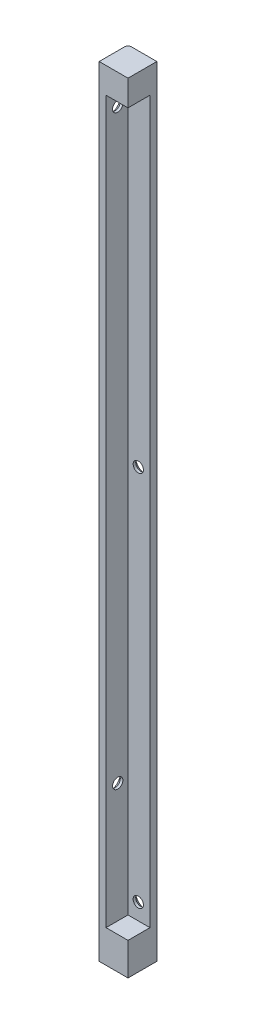
SolidWorks part; units mm, degrees
material "Aluminum"
ref_plane "Front Plane" through (0, 0, 0) normal (0, 0, 1) x (1, 0, 0)
ref_plane "Top Plane" through (0, 0, 0) normal (0, 1, 0) x (1, 0, 0)
ref_plane "Right Plane" through (0, 0, 0) normal (1, 0, 0) x (0, 0, -1)
sketch "Sketch1" plane through (0, 0, 0) normal (0, 1, 0) x (1, 0, 0)
  line L0 (0, 0) -> (0, 9)
  line L1 (0, 9) -> (9, 9)
  line L2 (2, 0) -> (2, 7)
  line L3 (2, 7) -> (9, 7)
  line L4 (9, 9) -> (9, 7)
  line L5 (0, 0) -> (2, 0)
  dimension "D1" = 9
  dimension "D2" = 9
  dimension "D3" = 2
extrude "Boss-Extrude1" add sketch "Sketch1" along normal blind 221.5
hole_wizard "CSK for M3 Countersunk Flat Head Screw1" positions "Sketch5" profile "Sketch4" countersink size "M3" standard "ISO" end condition through all
sketch "Sketch5" plane through (0, 0, 0) normal (-1, 0, 0) x (0, 0, 1)
  line L6 (-9, 221.5) -> (-9, 0) construction
  line L8 (-9, 110.75) -> (50.482, 110.75) construction
  point P16 (-4, 211)
  point P35 (-4, 40.25)
sketch "Sketch4" plane through (0, 211, -4) normal (0, 1, 0) x (0, 0, 1)
  line L0 (0, 0) -> (0, 9)
  line L1 (0, 9) -> (1.5, 9)
  line L2 (1.5, 9) -> (1.5, 1.25)
  line L3 (1.5, 1.25) -> (2.75, 0)
  line L5 (2.75, 0) -> (0, 0)
  line L6 (-1.5, 1.25) -> (-2.75, 0) construction
  line L11 (0, -6.35) -> (0, 107.95) construction
  dimension "Thru Hole Dia." = 3
  dimension "Thru Hole Depth" = 9
  dimension "Near C'Sink Dia." = 5.5
  dimension "Near C'Sink Angle" = 90
hole_wizard "CSK for M3 Countersunk Flat Head Screw4" positions "Sketch11" profile "Sketch10" countersink size "M3" standard "ISO" end condition through all
sketch "Sketch11" plane through (0, 0, -9) normal (0, 0, -1) x (-1, 0, 0)
  line L4 (0, 221.5) -> (0, 0) construction
  line L7 (0, 110.75) -> (77.647, 110.75) construction
  point P4 (-5, 10.25)
  point P33 (-5, 120)
sketch "Sketch10" plane through (5, 10.25, -9) normal (1, 0, 0) x (0, 1, 0)
  line L0 (0, 0) -> (0, 9)
  line L1 (0, 9) -> (1.5, 9)
  line L2 (1.5, 9) -> (1.5, 1.25)
  line L3 (1.5, 1.25) -> (2.75, 0)
  line L5 (2.75, 0) -> (0, 0)
  line L6 (-1.5, 1.25) -> (-2.75, 0) construction
  line L11 (0, -6.35) -> (0, 107.95) construction
  dimension "Thru Hole Dia." = 3
  dimension "Thru Hole Depth" = 9
  dimension "Near C'Sink Dia." = 5.5
  dimension "Near C'Sink Angle" = 90
sketch "Sketch12" plane through (0, 0, 0) normal (0, -1, 0) x (1, 0, 0)
  line L0 (2, -7) -> (9, -7) construction
  line L1 (1, -7) -> (9, -7)
  line L2 (1, -7) -> (1, 0)
  line L3 (1, 0) -> (9, 0)
  line L4 (9, -7) -> (9, 0)
  line L5 (9, -7) -> (9, -9) construction
extrude "Boss-Extrude2" add sketch "Sketch12" against normal blind 5.5
sketch "Sketch13" plane through (0, 221.5, 0) normal (0, 1, 0) x (1, 0, 0)
  line L0 (0, 8) -> (1, 9)
  line L1 (0, 9) -> (0, 0) construction
  line L2 (9, 9) -> (0, 9) construction
  line L3 (0, 8) -> (0, 9)
  line L4 (0, 9) -> (1, 9)
  dimension "D1" = 1
  dimension "D2" = 1
extrude "Cut-Extrude1" cut sketch "Sketch13" against normal blind 359
sketch "Sketch14" plane through (0, 0, 0) normal (0, -1, 0) x (1, 0, 0)
  line L0 (0, 0) -> (9, 0)
  line L1 (9, 0) -> (9, -9)
  line L2 (9, -9) -> (1, -9)
  line L3 (1, -9) -> (0, -8)
  line L4 (0, -8) -> (0, 0)
extrude "Boss-Extrude3" add sketch "Sketch14" along normal blind 3
sketch "Sketch18" plane through (0, 221.5, 0) normal (0, 1, 0) x (1, 0, 0)
  line L1 (0, 0) -> (9, 0)
  line L2 (0, 0) -> (0, 8)
  line L3 (1, 9) -> (9, 9)
  line L4 (9, 0) -> (9, 9)
  line L5 (1, 9) -> (0, 8)
  dimension "D1" = 9
  dimension "D2" = 9
extrude "Boss-Extrude4" add sketch "Sketch18" along normal blind 2.5 and the other way blind 6
sketch "Sketch19" plane through (0, 0, 0) normal (-1, 0, 0) x (0, 0, 1)
  line L1 (0, 224) -> (-0.6, 224)
  line L2 (0, 224) -> (0, -3)
  line L3 (0, -3) -> (-0.6, -3)
  line L4 (-0.6, 224) -> (-0.6, -3)
  line L5 (0, 224) -> (0, -3) construction
  dimension "D1" = 0.6
extrude "Cut-Extrude2" cut sketch "Sketch19" against normal blind 10
sketch "Sketch20" plane through (0, 0, 0) normal (-1, 0, 0) x (0, 0, 1)
  line L1 (-0.6, 224) -> (-16.2047, 224)
  line L2 (-0.6, 224) -> (-0.6, 222)
  line L3 (-0.6, 222) -> (-16.2047, 222)
  line L4 (-16.2047, 224) -> (-16.2047, 222)
  dimension "D1" = 2
extrude "Cut-Extrude3" cut sketch "Sketch20" against normal blind 10
sketch "Sketch21" plane through (0, 0, -9) normal (0, 0, -1) x (-1, 0, 0)
  line L0 (-1, -3) -> (-9, -3) construction
  line L1 (-9, 222) -> (-8.4, 222)
  line L2 (-9, 222) -> (-9, -3)
  line L3 (-9, -3) -> (-8.4, -3)
  line L4 (-8.4, 222) -> (-8.4, -3)
  dimension "D1" = 0.6
extrude "Cut-Extrude4" cut sketch "Sketch21" against normal blind 10
sketch "Sketch22" plane through (0, 0, -9) normal (0, 0, -1) x (-1, 0, 0)
  line L0 (0, -3) -> (0, 222) construction
  line L1 (-8.4, -3) -> (0, -3)
  line L2 (-8.4, -3) -> (-8.4, 2.5)
  line L3 (-8.4, 2.5) -> (0, 2.5)
  line L4 (0, -3) -> (0, 2.5)
  dimension "D1" = 5.5
extrude "Cut-Extrude5" cut sketch "Sketch22" against normal blind 10
sketch "Sketch26" plane through (0, 2.5, 0) normal (0, -1, 0) x (1, 0, 0)
  line L0 (8.4, -9) -> (8.4, -0.6)
  line L1 (8.4, -0.6) -> (0, -0.6)
  line L2 (0, -0.6) -> (0, -8)
  line L3 (0, -8) -> (1, -9)
  line L4 (1, -9) -> (8.4, -9)
extrude "Boss-Extrude5" add sketch "Sketch26" along normal blind 2
sketch "Sketch29" plane through (0, 222, 0) normal (0, 1, 0) x (1, 0, 0)
  line L0 (0, 8) -> (1, 9)
  line L1 (1, 9) -> (0, 9)
  line L2 (0, 9) -> (0, 8)
extrude "Boss-Extrude6" add sketch "Sketch29" against normal blind 221.5
fillet "Fillet1" radius 1 1 edges at (0, 111.25, -9)
sketch "Sketch30" plane through (0, 0.5, 0) normal (0, -1, 0) x (1, 0, 0)
  line L0 (0, -8) -> (0, -0.6)
  line L1 (0, -0.6) -> (8.4, -0.6)
  line L2 (8.4, -0.6) -> (8.4, -9)
  line L3 (8.4, -9) -> (1, -9)
  arc A0 (1, -9) -> (0, -8) centre (1, -8) cw
extrude "Boss-Extrude7" add sketch "Sketch30" along normal blind 4.5
sketch "Sketch31" plane through (0, 222, 0) normal (0, 1, 0) x (1, 0, 0)
  line L0 (0, 0.6) -> (8.4, 0.6)
  line L1 (8.4, 0.6) -> (8.4, 9)
  line L2 (8.4, 9) -> (1, 9)
  line L3 (0, 0.6) -> (0, 8)
  arc A0 (0, 8) -> (1, 9) centre (1, 8) cw
extrude "Boss-Extrude8" add sketch "Sketch31" along normal blind 1
